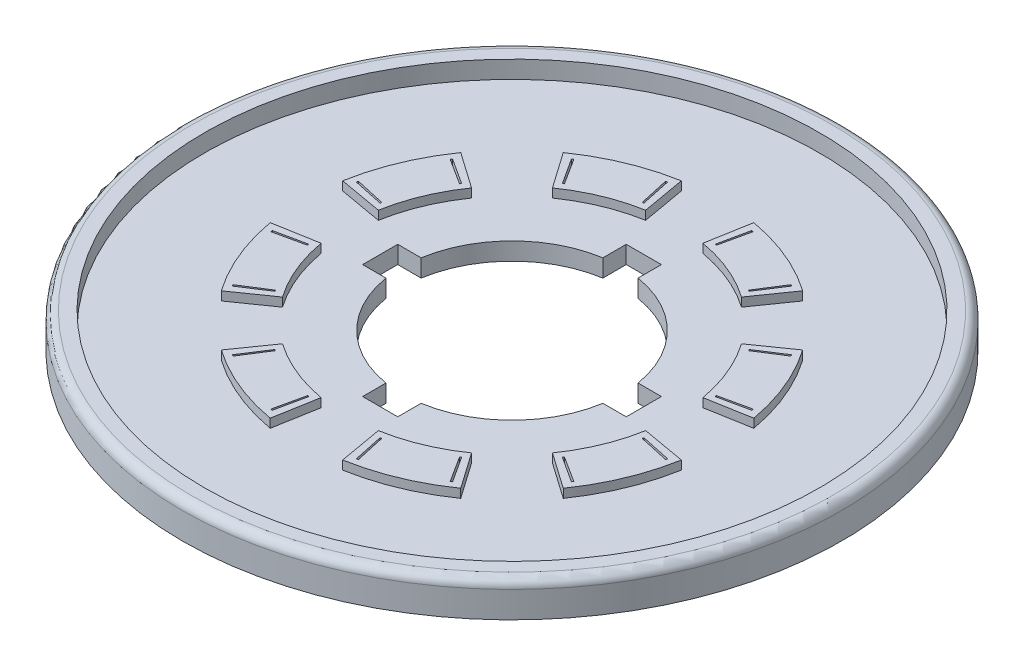
SolidWorks part; units mm, degrees
ref_plane "Alzado" through (0, 0, 0) normal (0, 0, 1) x (1, 0, 0)
ref_plane "Planta" through (0, 0, 0) normal (0, 1, 0) x (1, 0, 0)
ref_plane "Vista lateral" through (0, 0, 0) normal (1, 0, 0) x (0, 0, -1)
sketch "Croquis1" plane through (0, 0, 0) normal (0, 1, 0) x (1, 0, 0)
  circle A0 centre (0, 0) radius 75
  dimension "D1" = 150
extrude "Saliente-Extruir1" add sketch "Croquis1" along normal blind 4
sketch "Croquis3" plane through (0, 4, 0) normal (0, 1, 0) x (1, 0, 0)
  line L0 (-70, 0) -> (70, 0) construction
  line L1 (0, -70) -> (0, 70) construction
  line L3 (-49.4975, -49.4975) -> (49.4975, 49.4975) construction
  line L5 (-49.4975, 49.4975) -> (49.4975, -49.4975) construction
  circle A0 centre (0, 0) radius 75
  circle A1 centre (0, 0) radius 70
  dimension "D1" = 150
  dimension "D2" = 5
extrude "Saliente-Extruir2" add sketch "Croquis3" along normal blind 4
sketch "Croquis7" plane through (0, 4, 0) normal (0, 1, 0) x (1, 0, 0)
  line L0 (51.6188, -52.6795) -> (52.6795, -51.6188)
  line L9 (73.75, -0.75) -> (-73.75, -0.75)
  line L10 (73.75, -0.75) -> (73.75, 0.75)
  line L11 (73.75, 0.75) -> (-73.75, 0.75)
  line L12 (-73.75, -0.75) -> (-73.75, 0.75)
  line L13 (73.75, -0.75) -> (-73.75, 0.75) construction
  line L14 (73.75, 0.75) -> (-73.75, -0.75) construction
  line L15 (51.6188, -52.6795) -> (-52.6795, 51.6188)
  line L16 (-52.6795, 51.6188) -> (-51.6188, 52.6795)
  line L17 (52.6795, -51.6188) -> (-51.6188, 52.6795)
  line L18 (-0.75, -73.75) -> (0.75, -73.75)
  line L19 (-0.75, -73.75) -> (-0.75, 73.75)
  line L20 (-0.75, 73.75) -> (0.75, 73.75)
  line L21 (0.75, -73.75) -> (0.75, 73.75)
  line L22 (-52.6795, -51.6188) -> (-51.6188, -52.6795)
  line L23 (-52.6795, -51.6188) -> (51.6188, 52.6795)
  line L24 (51.6188, 52.6795) -> (52.6795, 51.6188)
  line L25 (-51.6188, -52.6795) -> (52.6795, 51.6188)
  line L26 (-73.75, 0.75) -> (-73.75, -0.75)
  line L27 (-73.75, 0.75) -> (73.75, 0.75)
  line L28 (73.75, 0.75) -> (73.75, -0.75)
  line L29 (-73.75, -0.75) -> (73.75, -0.75)
  point P0 (0, 0)
  point P25 (0, 0)
  dimension "D1" = 1.5
  dimension "D2" = 147.5
  dimension "D3" = 5
sketch "Croquis2" plane through (0, 0, 0) normal (0, -1, 0) x (1, 0, 0)
  line L0 (0, 0) -> (-75, 0) construction
  line L2 (0, 0) -> (-69.291, 28.7013) construction
  circle A0 centre (0, 0) radius 75 construction
  circle A1 centre (-55.4328, 22.961) radius 2.5
  circle A2 centre (-22.961, 55.4328) radius 2.5
  circle A3 centre (22.961, 55.4328) radius 2.5
  circle A4 centre (55.4328, 22.961) radius 2.5
  circle A5 centre (55.4328, -22.961) radius 2.5
  circle A6 centre (22.961, -55.4328) radius 2.5
  circle A7 centre (-22.961, -55.4328) radius 2.5
  circle A8 centre (-55.4328, -22.961) radius 2.5
  point P25 (0, 0)
  dimension "D1" = 5
  dimension "D2" = 60
  dimension "D4" = 22.5
  dimension "D3" = 8
extrude "Saliente-Extruir3" [suppressed] add sketch "Croquis7" along normal blind 1 contours L11 L19 L17 L15 | L11 L12 L9 L10 | L21 L20 L19 L18 | L23 L24 L25 L22 | L15 L16 L17 L0
extrude "Cortar-Extruir1" cut sketch "Croquis2" against normal blind 2
sketch "Croquis4" plane through (0, 0, 0) normal (0, -1, 0) x (1, 0, 0)
  circle A0 centre (0, 0) radius 25
  dimension "D1" = 50
extrude "Cortar-Extruir2" cut sketch "Croquis4" against normal blind 6
sketch "Croquis8" plane through (0, 4, 0) normal (0, 1, 0) x (1, 0, 0)
  line L0 (-46.7784, -8.2483) -> (-36.9303, -6.5118)
  line L1 (-38.9097, -27.2449) -> (-30.7182, -21.5091)
  line L3 (-38.9097, 27.2449) -> (-30.7182, 21.5091)
  line L5 (-46.7784, 8.2483) -> (-36.9303, 6.5118)
  line L6 (-8.2483, 46.7784) -> (-6.5118, 36.9303)
  line L7 (-27.2449, 38.9097) -> (-21.5091, 30.7182)
  line L8 (27.2449, 38.9097) -> (21.5091, 30.7182)
  line L9 (8.2483, 46.7784) -> (6.5118, 36.9303)
  line L10 (46.7784, 8.2483) -> (36.9303, 6.5118)
  line L11 (38.9097, 27.2449) -> (30.7182, 21.5091)
  line L12 (38.9097, -27.2449) -> (30.7182, -21.5091)
  line L13 (46.7784, -8.2483) -> (36.9303, -6.5118)
  line L14 (8.2483, -46.7784) -> (6.5118, -36.9303)
  line L15 (27.2449, -38.9097) -> (21.5091, -30.7182)
  line L16 (-27.2449, -38.9097) -> (-21.5091, -30.7182)
  line L17 (-8.2483, -46.7784) -> (-6.5118, -36.9303)
  line L20 (0, 0) -> (-75, 0) construction
  circle A0 centre (0, 0) radius 37.5 construction
  circle A1 centre (0, 0) radius 47.5 construction
  arc A2 (-36.9303, -6.5118) -> (-30.7182, -21.5091) centre (0, 0) ccw
  arc A3 (-38.9097, -27.2449) -> (-46.7784, -8.2483) centre (0, 0) cw
  arc A4 (-46.7784, 8.2483) -> (-38.9097, 27.2449) centre (0, 0) cw
  arc A5 (-30.7182, 21.5091) -> (-36.9303, 6.5118) centre (0, 0) ccw
  arc A6 (-27.2449, 38.9097) -> (-8.2483, 46.7784) centre (0, 0) cw
  arc A7 (-6.5118, 36.9303) -> (-21.5091, 30.7182) centre (0, 0) ccw
  arc A8 (8.2483, 46.7784) -> (27.2449, 38.9097) centre (0, 0) cw
  arc A9 (21.5091, 30.7182) -> (6.5118, 36.9303) centre (0, 0) ccw
  arc A10 (38.9097, 27.2449) -> (46.7784, 8.2483) centre (0, 0) cw
  arc A11 (36.9303, 6.5118) -> (30.7182, 21.5091) centre (0, 0) ccw
  arc A12 (46.7784, -8.2483) -> (38.9097, -27.2449) centre (0, 0) cw
  arc A13 (30.7182, -21.5091) -> (36.9303, -6.5118) centre (0, 0) ccw
  arc A14 (27.2449, -38.9097) -> (8.2483, -46.7784) centre (0, 0) cw
  arc A15 (6.5118, -36.9303) -> (21.5091, -30.7182) centre (0, 0) ccw
  arc A16 (-8.2483, -46.7784) -> (-27.2449, -38.9097) centre (0, 0) cw
  arc A17 (-21.5091, -30.7182) -> (-6.5118, -36.9303) centre (0, 0) ccw
  circle A52 centre (0, 0) radius 75 construction
  point P45 (0, 0)
  point P115 (0, 0)
  dimension "D1" = 75
  dimension "D2" = 95
  dimension "D3" = 10
  dimension "D4" = 25
  dimension "D5" = 8
extrude "Saliente-Extruir4" add sketch "Croquis8" along normal blind 2
sketch "Croquis10" plane through (0, 6, 0) normal (0, 1, 0) x (1, 0, 0)
  line L0 (-44.9948, -9.5639) -> (-38.1478, -8.1086)
  line L1 (-44.9096, -9.9562) -> (-38.0755, -8.4411)
  line L2 (-36.9303, -6.5118) -> (-46.7784, -8.2483) construction
  line L3 (0, 0) -> (-43.8843, -18.1775) construction
  line L4 (-38.5788, -25.0534) -> (-32.7082, -21.2409)
  line L5 (-38.796, -24.7158) -> (-32.8923, -20.9547)
  line L6 (-38.796, 24.7158) -> (-32.8923, 20.9547)
  line L7 (-38.5788, 25.0534) -> (-32.7082, 21.2409)
  line L8 (-44.9948, 9.5639) -> (-38.1478, 8.1086)
  line L9 (-44.9096, 9.9562) -> (-38.0755, 8.4411)
  line L10 (-9.9562, 44.9096) -> (-8.4411, 38.0755)
  line L11 (-9.5639, 44.9948) -> (-8.1086, 38.1478)
  line L12 (-25.0534, 38.5788) -> (-21.2409, 32.7082)
  line L13 (-24.7158, 38.796) -> (-20.9547, 32.8923)
  line L14 (24.7158, 38.796) -> (20.9547, 32.8923)
  line L15 (25.0534, 38.5788) -> (21.2409, 32.7082)
  line L16 (9.5639, 44.9948) -> (8.1086, 38.1478)
  line L17 (9.9562, 44.9096) -> (8.4411, 38.0755)
  line L18 (44.9096, 9.9562) -> (38.0755, 8.4411)
  line L19 (44.9948, 9.5639) -> (38.1478, 8.1086)
  line L20 (38.5788, 25.0534) -> (32.7082, 21.2409)
  line L21 (38.796, 24.7158) -> (32.8923, 20.9547)
  line L22 (38.796, -24.7158) -> (32.8923, -20.9547)
  line L23 (38.5788, -25.0534) -> (32.7082, -21.2409)
  line L24 (44.9948, -9.5639) -> (38.1478, -8.1086)
  line L25 (44.9096, -9.9562) -> (38.0755, -8.4411)
  line L26 (9.9562, -44.9096) -> (8.4411, -38.0755)
  line L27 (9.5639, -44.9948) -> (8.1086, -38.1478)
  line L28 (25.0534, -38.5788) -> (21.2409, -32.7082)
  line L29 (24.7158, -38.796) -> (20.9547, -32.8923)
  line L30 (-24.7158, -38.796) -> (-20.9547, -32.8923)
  line L31 (-25.0534, -38.5788) -> (-21.2409, -32.7082)
  line L32 (-9.5639, -44.9948) -> (-8.1086, -38.1478)
  line L33 (-9.9562, -44.9096) -> (-8.4411, -38.0755)
  circle A0 centre (0, 0) radius 39 construction
  circle A1 centre (0, 0) radius 46 construction
  arc A2 (-36.9303, -6.5118) -> (-30.7182, -21.5091) centre (0, 0) ccw construction
  arc A3 (-46.7784, -8.2483) -> (-38.9097, -27.2449) centre (0, 0) ccw construction
  arc A4 (-38.1478, -8.1086) -> (-38.0755, -8.4411) centre (0, 0) ccw
  arc A5 (-44.9948, -9.5639) -> (-44.9096, -9.9562) centre (0, 0) ccw
  arc A6 (-32.7082, -21.2409) -> (-32.8923, -20.9547) centre (0, 0) cw
  arc A7 (-38.5788, -25.0534) -> (-38.796, -24.7158) centre (0, 0) cw
  arc A8 (-38.5788, 25.0534) -> (-38.796, 24.7158) centre (0, 0) ccw
  arc A9 (-32.7082, 21.2409) -> (-32.8923, 20.9547) centre (0, 0) ccw
  arc A10 (-38.1478, 8.1086) -> (-38.0755, 8.4411) centre (0, 0) cw
  arc A11 (-44.9948, 9.5639) -> (-44.9096, 9.9562) centre (0, 0) cw
  arc A12 (-9.5639, 44.9948) -> (-9.9562, 44.9096) centre (0, 0) ccw
  arc A13 (-8.1086, 38.1478) -> (-8.4411, 38.0755) centre (0, 0) ccw
  arc A14 (-21.2409, 32.7082) -> (-20.9547, 32.8923) centre (0, 0) cw
  arc A15 (-25.0534, 38.5788) -> (-24.7158, 38.796) centre (0, 0) cw
  arc A16 (25.0534, 38.5788) -> (24.7158, 38.796) centre (0, 0) ccw
  arc A17 (21.2409, 32.7082) -> (20.9547, 32.8923) centre (0, 0) ccw
  arc A18 (8.1086, 38.1478) -> (8.4411, 38.0755) centre (0, 0) cw
  arc A19 (9.5639, 44.9948) -> (9.9562, 44.9096) centre (0, 0) cw
  arc A20 (44.9948, 9.5639) -> (44.9096, 9.9562) centre (0, 0) ccw
  arc A21 (38.1478, 8.1086) -> (38.0755, 8.4411) centre (0, 0) ccw
  arc A22 (32.7082, 21.2409) -> (32.8923, 20.9547) centre (0, 0) cw
  arc A23 (38.5788, 25.0534) -> (38.796, 24.7158) centre (0, 0) cw
  arc A24 (38.5788, -25.0534) -> (38.796, -24.7158) centre (0, 0) ccw
  arc A25 (32.7082, -21.2409) -> (32.8923, -20.9547) centre (0, 0) ccw
  arc A26 (38.1478, -8.1086) -> (38.0755, -8.4411) centre (0, 0) cw
  arc A27 (44.9948, -9.5639) -> (44.9096, -9.9562) centre (0, 0) cw
  arc A28 (9.5639, -44.9948) -> (9.9562, -44.9096) centre (0, 0) ccw
  arc A29 (8.1086, -38.1478) -> (8.4411, -38.0755) centre (0, 0) ccw
  arc A30 (21.2409, -32.7082) -> (20.9547, -32.8923) centre (0, 0) cw
  arc A31 (25.0534, -38.5788) -> (24.7158, -38.796) centre (0, 0) cw
  arc A32 (-25.0534, -38.5788) -> (-24.7158, -38.796) centre (0, 0) ccw
  arc A33 (-21.2409, -32.7082) -> (-20.9547, -32.8923) centre (0, 0) ccw
  arc A34 (-8.1086, -38.1478) -> (-8.4411, -38.0755) centre (0, 0) cw
  arc A35 (-9.5639, -44.9948) -> (-9.9562, -44.9096) centre (0, 0) cw
  point P82 (0, 0)
  dimension "D1" = 1.5
  dimension "D2" = 1.5
  dimension "D3" = 2
  dimension "D4" = 0.5
  dimension "D5" = 8
extrude "Cortar-Extruir3" cut sketch "Croquis10" against normal blind 11
fillet "Redondeo1" radius 2 1 edges at (0, 8, 75)
sketch "Croquis11" plane through (0, 4, 0) normal (0, 1, 0) x (1, 0, 0)
  line L0 (-4, -30) -> (4, -30)
  line L1 (30, -4) -> (-30, -4)
  line L2 (30, -4) -> (30, 4)
  line L3 (30, 4) -> (-30, 4)
  line L4 (-30, -4) -> (-30, 4)
  line L5 (30, -4) -> (-30, 4) construction
  line L6 (30, 4) -> (-30, -4) construction
  line L7 (-4, -30) -> (-4, 30)
  line L8 (-4, 30) -> (4, 30)
  line L9 (4, -30) -> (4, 30)
  point P0 (0, 0)
  point P13 (0, 0)
  circle M1 centre (0, 0) radius 25
  dimension "D1" = 60
  dimension "D2" = 8
  dimension "D3" = 2
extrude "Cortar-Extruir4" cut sketch "Croquis11" against normal blind 10 contours L4 L1 L3 M1 | L9 L8 L7 M1 | L2 L3 L1 M1 | L0 L9 L7 M1 region at (0, 4, 27.4456) region at (-27.4456, 4, 0) region at (27.4456, 4, 0) region at (0, 4, -27.4456)
